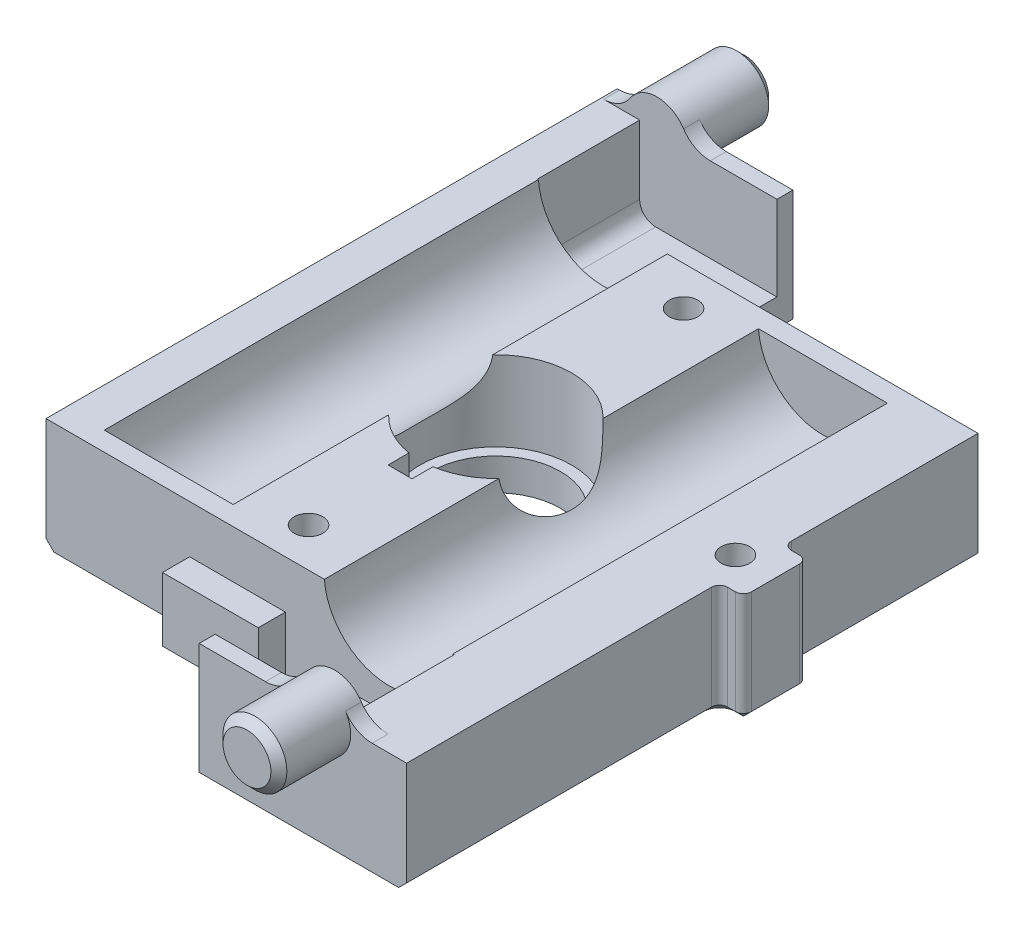
SolidWorks part; units mm, degrees
ref_plane "Front Plane" through (0, 0, 0) normal (0, 0, 1) x (1, 0, 0)
ref_plane "Top Plane" through (0, 0, 0) normal (0, 1, 0) x (1, 0, 0)
ref_plane "Right Plane" through (0, 0, 0) normal (1, 0, 0) x (0, 0, -1)
sketch "Sketch1" plane through (0, 0, 0) normal (0, 1, 0) x (1, 0, 0)
  line L1 (-61.4569, -66.3705) -> (-31.4569, -66.3705)
  line L2 (-61.4569, -66.3705) -> (-61.4569, -35.5705)
  line L3 (-61.4569, -35.5705) -> (-31.4569, -35.5705)
  line L4 (-31.4569, -66.3705) -> (-31.4569, -35.5705)
  dimension "D1" = 30.8
  dimension "D2" = 30
extrude "Boss-Extrude1" add sketch "Sketch1" along normal blind 7
sketch "Sketch2" plane through (0, 0, 0) normal (0, -1, 0) x (1, 0, 0)
  circle A0 centre (-47.4719, 50.9705) radius 4.05
  dimension "D1" = 8.1
extrude "Cut-Extrude1" cut sketch "Sketch2" against normal blind 6.5
sketch "Sketch3" plane through (0, 0, 0) normal (0, -1, 0) x (1, 0, 0)
  line L1 (-31.4569, 66.3705) -> (-46.4569, 66.3705)
  line L2 (-31.4569, 66.3705) -> (-31.4569, 65.1705)
  line L3 (-31.4569, 65.1705) -> (-46.4569, 65.1705)
  line L4 (-46.4569, 66.3705) -> (-46.4569, 65.1705)
  line L5 (-61.4569, 66.3705) -> (-52.4569, 66.3705)
  line L6 (-61.4569, 66.3705) -> (-61.4569, 65.1705)
  line L7 (-61.4569, 65.1705) -> (-52.4569, 65.1705)
  line L8 (-52.4569, 66.3705) -> (-52.4569, 65.1705)
  line L9 (-31.4569, 35.5705) -> (-42.4569, 35.5705)
  line L10 (-31.4569, 35.5705) -> (-31.4569, 36.7705)
  line L11 (-31.4569, 36.7705) -> (-42.4569, 36.7705)
  line L12 (-42.4569, 35.5705) -> (-42.4569, 36.7705)
  line L13 (-61.4569, 35.5705) -> (-48.4569, 35.5705)
  line L14 (-61.4569, 35.5705) -> (-61.4569, 36.7705)
  line L15 (-61.4569, 36.7705) -> (-48.4569, 36.7705)
  line L16 (-48.4569, 35.5705) -> (-48.4569, 36.7705)
  dimension "D1" = 15
  dimension "D2" = 9
  dimension "D3" = 1.2
  dimension "D4" = 1.2
  dimension "D5" = 1.2
  dimension "D6" = 1.2
  dimension "D7" = 11
  dimension "D8" = 13
extrude "Cut-Extrude2" cut sketch "Sketch3" against normal blind 4
sketch "Sketch4" plane through (0, 0, 66.3705) normal (0, 0, 1) x (1, 0, 0)
  line L1 (-61.4569, 7) -> (-31.4569, 7)
  line L2 (-61.4569, 7) -> (-61.4569, 4)
  line L3 (-61.4569, 4) -> (-31.4569, 4)
  line L4 (-31.4569, 7) -> (-31.4569, 4)
extrude "Cut-Extrude3" cut sketch "Sketch4" against normal blind 1.2
sketch "Sketch5" plane through (0, 0, 35.5705) normal (0, 0, -1) x (-1, 0, 0)
  line L1 (61.4569, 4) -> (31.4569, 4)
  line L2 (61.4569, 4) -> (61.4569, 7)
  line L3 (61.4569, 7) -> (31.4569, 7)
  line L4 (31.4569, 4) -> (31.4569, 7)
extrude "Cut-Extrude4" cut sketch "Sketch5" against normal blind 1.2
sketch "Sketch6" plane through (0, 0, 65.1705) normal (0, 0, 1) x (1, 0, 0)
  line L0 (-44.0746, 7.3) -> (-35.8746, 7.3) construction
  circle A0 centre (-39.9746, 7.3) radius 4.05
  dimension "D1" = 8.1
extrude "Cut-Extrude5" cut sketch "Sketch6" against normal blind 27.2
sketch "Sketch7" plane through (0, 0, 36.7705) normal (0, 0, -1) x (-1, 0, 0)
  line L0 (50.8646, 7.3) -> (59.0646, 7.3) construction
  circle A0 centre (54.9646, 7.3) radius 4.05
  dimension "D1" = 8.1
extrude "Cut-Extrude6" cut sketch "Sketch7" against normal blind 27.2
sketch "Sketch8" plane through (0, 7, 0) normal (0, 1, 0) x (1, 0, 0)
  circle A0 centre (-47.4719, -50.9705) radius 4.75
  dimension "D1" = 9.5
extrude "Cut-Extrude7" cut sketch "Sketch8" against normal blind 5
sketch "Sketch10" plane through (0, 0, 65.1705) normal (0, 0, 1) x (1, 0, 0)
  line L5 (-31.4569, 0) -> (-31.4569, 7)
  line L6 (-31.4569, 7) -> (-35.8569, 7)
  line L7 (-31.4569, 7) -> (-35.9357, 7) construction
  line L8 (-35.8569, 7) -> (-35.8569, 1.7)
  line L9 (-35.8569, 1.7) -> (-44.4569, 1.7)
  line L10 (-44.4569, 1.7) -> (-44.4569, 0)
  line L11 (-46.4569, 0) -> (-31.4569, 0) construction
  line L12 (-44.4569, 0) -> (-31.4569, 0)
  dimension "D1" = 4.4
  dimension "D2" = 1.7
  dimension "D3" = 13
extrude "Boss-Extrude2" add sketch "Sketch10" along normal blind 6.4
fillet "Fillet1" radius 1 1 edges at (-35.8569, 1.7, 68.3705)
sketch "Sketch11" plane through (0, 0, 36.7705) normal (0, 0, -1) x (-1, 0, 0)
  line L0 (61.4569, 7) -> (61.4569, 0)
  line L1 (61.4569, 0) -> (50.4569, 0)
  line L2 (48.4569, 0) -> (61.4569, 0) construction
  line L3 (50.4569, 0) -> (50.4569, 1.7)
  line L4 (50.4569, 1.7) -> (59.0569, 1.7)
  line L5 (59.0569, 1.7) -> (59.0569, 7)
  line L6 (61.4569, 7) -> (59.0034, 7) construction
  line L7 (59.0569, 7) -> (61.4569, 7)
  dimension "D1" = 2.4
  dimension "D2" = 1.7
  dimension "D3" = 11
extrude "Boss-Extrude3" add sketch "Sketch11" along normal blind 6.4
fillet "Fillet2" radius 1 1 edges at (-59.0569, 1.7, 33.5705)
sketch "Sketch12" plane through (0, 7, 0) normal (0, 1, 0) x (1, 0, 0)
  line L1 (-46.7219, -56.9705) -> (-48.2219, -56.9705)
  line L2 (-46.7219, -56.9705) -> (-46.7219, -55.6264)
  line L3 (-46.7219, -55.6264) -> (-48.2219, -55.6264)
  line L4 (-48.2219, -56.9705) -> (-48.2219, -55.6264)
  arc A0 (-46.9719, -55.5935) -> (-47.9719, -55.5935) centre (-47.4719, -50.9705) ccw construction
  dimension "D1" = 1.5
  dimension "D2" = 0.75
  dimension "D3" = 6
extrude "Cut-Extrude8" cut sketch "Sketch12" against normal up to surface (5 mm away) up to face at (-47.4719, 2, 55.7205)
sketch "Sketch13" plane through (0, 0, 71.5705) normal (0, 0, 1) x (1, 0, 0)
  line L0 (-44.0134, 7) -> (-61.4569, 7) construction
  line L1 (-31.4569, 0) -> (-44.4569, 0)
  line L2 (-31.4569, 0) -> (-31.4569, 7)
  line L3 (-31.4569, 7) -> (-44.4569, 7)
  line L4 (-44.4569, 0) -> (-44.4569, 7)
extrude "Boss-Extrude4" add sketch "Sketch13" along normal blind 1
sketch "Sketch14" plane through (0, 0, 30.3705) normal (0, 0, -1) x (-1, 0, 0)
  line L0 (50.9257, 7) -> (31.4569, 7) construction
  line L1 (61.4569, 0) -> (50.4569, 0)
  line L2 (61.4569, 0) -> (61.4569, 7)
  line L3 (61.4569, 7) -> (50.4569, 7)
  line L4 (50.4569, 0) -> (50.4569, 7)
extrude "Boss-Extrude5" add sketch "Sketch14" along normal blind 1
sketch "Sketch15" plane through (0, 0, 71.5705) normal (0, 0, 1) x (1, 0, 0)
  circle A0 centre (-36.9646, 6.8) radius 2
  dimension "D1" = 4
sketch "Sketch16" plane through (0, 0, 30.3705) normal (0, 0, -1) x (-1, 0, 0)
  circle A0 centre (57.9746, 6.8) radius 2
  dimension "D1" = 4
extrude "Boss-Extrude8" add sketch "Sketch15" along normal blind 5.5
extrude "Boss-Extrude9" add sketch "Sketch16" along normal blind 5.5
fillet "Fillet3" radius 2 1 edges at (-59.9645, 7, 29.8705)
fillet "Fillet4" radius 2 1 edges at (-55.9846, 7, 29.8705)
fillet "Fillet5" radius 2 2 edges at (-34.9746, 7, 72.0705) (-38.9545, 7, 72.0705)
chamfer "Chamfer2" distance 0.5 angle 45 1 edges at (-34.9646, 6.8, 77.0705)
chamfer "Chamfer3" distance 0.5 angle 45 1 edges at (-59.9746, 6.8, 24.8705)
sketch "Sketch17" plane through (-31.4569, 0, 0) normal (1, 0, 0) x (0, 0, -1)
  line L0 (-72.5705, 7) -> (-36.7705, 7) construction
  line L1 (-52.9705, 7) -> (-48.9705, 7)
  line L2 (-52.9705, 7) -> (-52.9705, 0)
  line L3 (-52.9705, 0) -> (-48.9705, 0)
  line L4 (-48.9705, 7) -> (-48.9705, 0)
  line L5 (-72.5705, 0) -> (-36.7705, 0) construction
  line L6 (-36.7705, 7) -> (-36.7705, 0) construction
  dimension "D1" = 4
  dimension "D2" = 12.2
extrude "Boss-Extrude10" add sketch "Sketch17" along normal blind 1.5
fillet "Fillet7" radius 0.5 4 edges at (-31.4569, 3.5, 52.9705) (-29.9569, 3.5, 52.9705) (-29.9569, 3.5, 48.9705) (-31.4569, 3.5, 48.9705)
sketch "Sketch18" plane through (0, 0, 0) normal (0, -1, 0) x (1, 0, 0)
  circle A0 centre (-32.4569, 50.9705) radius 0.9
  dimension "D1" = 1.8
extrude "Cut-Extrude9" cut sketch "Sketch18" against normal through all
sketch "Sketch19" plane through (0, 0, 0) normal (0, -1, 0) x (1, 0, 0)
  circle A0 centre (-32.4569, 50.9705) radius 1.6
  dimension "D1" = 3.2
extrude "Cut-Extrude10" cut sketch "Sketch19" against normal blind 2
sketch "Sketch20" plane through (0, 0, 0) normal (0, -1, 0) x (1, 0, 0)
  circle A0 centre (-47.4569, 62.7205) radius 0.9
  circle A1 centre (-47.4569, 39.2205) radius 0.9
  dimension "D1" = 1.8
  dimension "D2" = 1.8
extrude "Cut-Extrude11" cut sketch "Sketch20" against normal through all
sketch "Sketch21" plane through (0, 0, 0) normal (0, -1, 0) x (1, 0, 0)
  circle A0 centre (-47.4569, 62.7205) radius 1.6
  circle A1 centre (-47.4569, 39.2205) radius 1.6
  dimension "D1" = 3.2
  dimension "D2" = 3.2
extrude "Cut-Extrude12" cut sketch "Sketch21" against normal blind 2
chamfer "Chamfer6" distance 0.5 angle 45 10 edges at (-61.4569, 0, 47.2705) (-31.4569, 0, 42.6205) (-31.3104, 0, 48.8241) (-30.7069, 0, 48.9705) (-30.1033, 0, 49.117) (-29.9569, 0, 50.9705) (-30.1033, 0, 52.8241) (-30.7069, 0, 52.9705) (-31.3104, 0, 53.117) (-31.4569, 0, 63.0205)
sketch "Sketch22" plane through (0, 0, 35.5705) normal (0, 0, -1) x (-1, 0, 0)
  line L1 (42.4569, 4) -> (48.4569, 4)
  line L2 (42.4569, 4) -> (42.4569, 0)
  line L3 (42.4569, 0) -> (48.4569, 0)
  line L4 (48.4569, 4) -> (48.4569, 0)
extrude "Boss-Extrude11" add sketch "Sketch22" along normal blind 0.5
sketch "Sketch23" plane through (0, 0, 66.3705) normal (0, 0, 1) x (1, 0, 0)
  line L1 (-52.4569, 4) -> (-46.4569, 4)
  line L2 (-52.4569, 4) -> (-52.4569, 0)
  line L3 (-52.4569, 0) -> (-46.4569, 0)
  line L4 (-46.4569, 4) -> (-46.4569, 0)
extrude "Boss-Extrude12" add sketch "Sketch23" along normal blind 0.5
